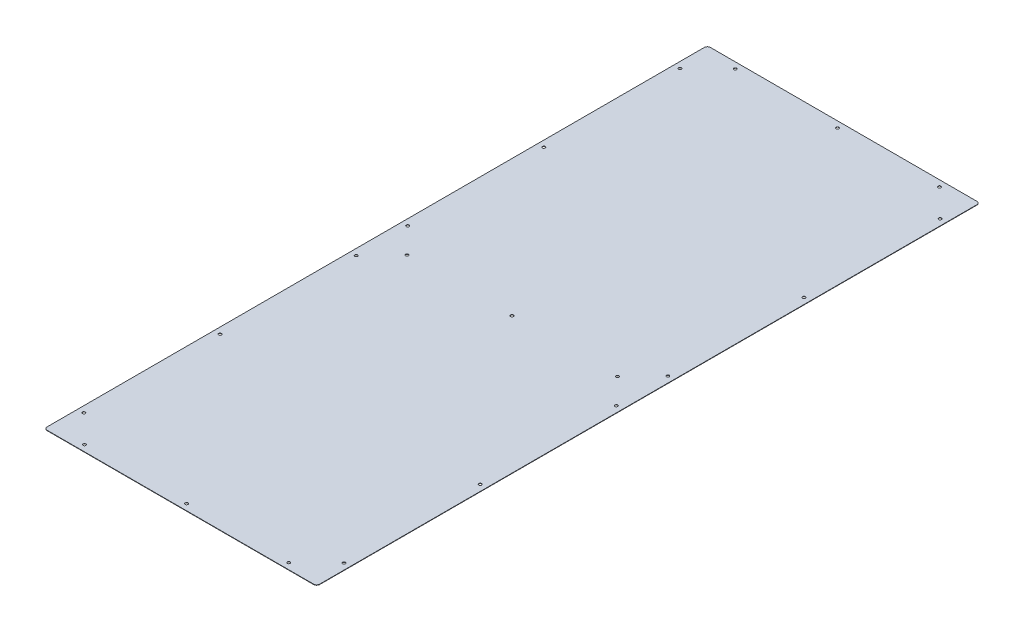
SolidWorks part; units mm, degrees
ref_plane "Front Plane" through (0, 0, 0) normal (0, 0, 1) x (1, 0, 0)
ref_plane "Top Plane" through (0, 0, 0) normal (0, 1, 0) x (1, 0, 0)
ref_plane "Right Plane" through (0, 0, 0) normal (1, 0, 0) x (0, 0, -1)
sketch "Sketch1" plane through (0, 0, 0) normal (0, 1, 0) x (1, 0, 0)
  line L1 (-279.5524, -680.3644) -> (279.5524, -680.3644)
  line L2 (-279.5524, -680.3644) -> (-279.5524, 680.3644)
  line L3 (-279.5524, 680.3644) -> (279.5524, 680.3644)
  line L4 (279.5524, -680.3644) -> (279.5524, 680.3644)
  line L5 (-279.5524, -680.3644) -> (279.5524, 680.3644) construction
  line L6 (-279.5524, 680.3644) -> (279.5524, -680.3644) construction
  point P0 (0, 0)
  dimension "D1" = 1360.7288
  dimension "D2" = 559.1048
extrude "Boss-Extrude1" add sketch "Sketch1" along normal blind 0.7937
fillet "Fillet1" radius 6.35 4 edges at (-279.5524, 0.3969, -680.3644) (279.5524, 0.3969, -680.3644) (-279.5524, 0.3969, 680.3644) (279.5524, 0.3969, 680.3644)
hole_wizard "#1 (0.228) Diameter Hole1" positions "Sketch2" profile "Sketch3" hole size "#1" standard "ANSI Inch" end condition through all
sketch "Sketch2" plane through (0, 0, 0) normal (0, -1, 0) x (-1, 0, 0)
  point P0 (-266.8524, -611.632)
  point P3 (-209.55, -667.6644)
  point P6 (-266.8524, -332.232)
  point P9 (0, -667.6644)
  point P12 (209.55, -667.6644)
  point P15 (266.8524, -611.632)
  point P18 (266.8524, -332.232)
  point P21 (0, 0)
  point P24 (215.7476, 0.1524)
  point P27 (266.8524, -52.832)
  point P30 (266.8524, 52.832)
  point P33 (-266.8524, -52.832)
  point P35 (-266.8524, 52.832)
  point P38 (-216.0524, 0.1524)
  point P41 (-266.8524, 332.232)
  point P44 (-266.8524, 611.632)
  point P47 (-209.55, 667.6644)
  point P50 (0, 667.6644)
  point P53 (266.8524, 332.232)
  point P56 (266.8524, 611.632)
  point P58 (209.55, 667.6644)
sketch "Sketch3" plane through (266.8524, 0, 611.632) normal (1, 0, 0) x (0, 0, -1)
  line L0 (0, 0) -> (0, 0.7937)
  line L1 (0, 0.7937) -> (2.8956, 0.7937)
  line L2 (2.8956, 0.7937) -> (2.8956, 0)
  line L5 (2.8956, 0) -> (0, 0)
  line L11 (0, -6.35) -> (0, 107.95) construction
  dimension "Thru Hole Dia." = 5.7912
  dimension "Thru Hole Depth" = 0.7937
